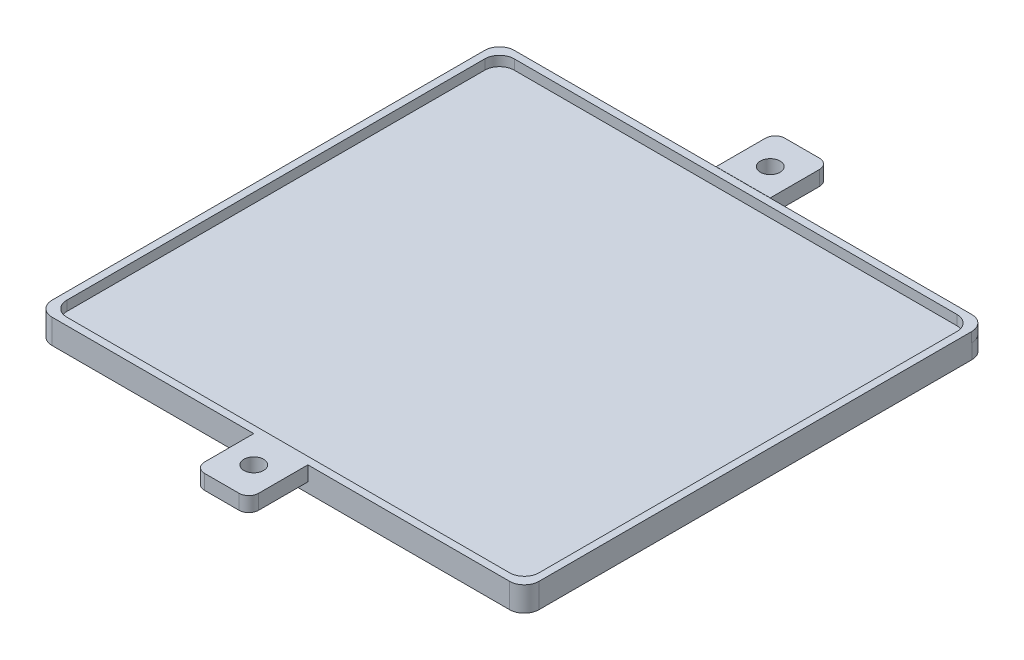
SolidWorks part; units mm, degrees
ref_plane "Plano frontal" through (0, 0, 0) normal (0, 0, 1) x (1, 0, 0)
ref_plane "Plano superior" through (0, 0, 0) normal (0, 1, 0) x (1, 0, 0)
ref_plane "Plano direito" through (0, 0, 0) normal (1, 0, 0) x (0, 0, -1)
sketch "Esboço1" plane through (0, 0, 0) normal (0, 1, 0) x (1, 0, 0)
  line L0 (0, -3) -> (93, -3)
  line L1 (0, 0) -> (93, 0) construction
  line L2 (0, 0) -> (0, 88) construction
  line L3 (0, 88) -> (93, 88) construction
  line L4 (93, 0) -> (93, 88) construction
  line L5 (-3, 0) -> (-3, 88)
  line L6 (0, 91) -> (93, 91)
  line L7 (96, 0) -> (96, 88)
  line L13 (46.5, 88) -> (46.5, 0) construction
  line L15 (0, 44) -> (93, 44) construction
  line L20 (0, 0) -> (93, 88) construction
  line L24 (96, 38.5) -> (96, 49.5)
  line L25 (43, 103) -> (50, 103)
  line L26 (41, -3) -> (52, -3)
  line L27 (41, -3) -> (41, -13)
  line L28 (43, -15) -> (50, -15)
  line L29 (52, -3) -> (52, -13)
  line L30 (52, 91) -> (52, 101)
  line L31 (41, 91) -> (52, 91)
  line L32 (41, 91) -> (41, 101)
  arc A3 (93, -3) -> (96, 0) centre (93, 0) ccw
  arc A4 (93, 91) -> (96, 88) centre (93, 88) cw
  arc A5 (-3, 88) -> (0, 91) centre (0, 88) cw
  arc A6 (0, -3) -> (-3, 0) centre (0, 0) cw
  arc A16 (50, -15) -> (52, -13) centre (50, -13) ccw
  arc A17 (41, -13) -> (43, -15) centre (43, -13) ccw
  circle A18 centre (46.5, -8.5) radius 2
  circle A19 centre (46.5, 96.5) radius 2
  arc A20 (50, 103) -> (52, 101) centre (50, 101) cw
  arc A21 (41, 101) -> (43, 103) centre (43, 101) cw
  point P15 (96, -3)
  point P24 (96, 91)
  dimension "D10" = 2
  dimension "D7" = 41
  dimension "D8" = 3
  dimension "D11" = 10
  dimension "D12" = 5.5
  dimension "D1" = 93
  dimension "D2" = 88
  dimension "D3" = 99
  dimension "D4" = 94
  dimension "D5" = 3
  dimension "D6" = 3
  dimension "D9" = 41
  dimension "D13" = 5.5
extrude "Ressalto-extrusão2" add sketch "Esboço1" along normal blind 3 contours L0 L7 L6 L5 L4 L1 L2 L3 region at (46.5, 0, -44)
extrude "Ressalto-extrusão3" add sketch "Esboço1<8>" along normal blind 3 from offset 2 contours L27 A17 L28 A16 L29 L0 A18 | A21 L32 L6 L30 A20 L25 A19 region at (46.5, 0, 3.1628) region at (41.1628, 0, -96)
sketch "Esboço1<8>" plane through (0, 0, 0) normal (0, 1, 0) x (1, 0, 0) same geometry as "Esboço1"
sketch "Esboço2" plane through (0, 3, 0) normal (0, 1, 0) x (1, 0, 0)
  line L0 (-3, 88) -> (-3, 90.9604) construction
  line L5 (-3, 90.9604) -> (-0.4856, 90.9604) construction
  line L6 (93, -3) -> (96, -3) construction
  line L7 (96, -3) -> (96, 0) construction
  line L9 (0, 90.9604) -> (93, 90.9604)
  line L10 (-3, 87.9604) -> (-3, 0)
  line L11 (0, -3) -> (93, -3)
  line L12 (96, 87.9604) -> (96, 0)
  line L13 (1.5, 89.4604) -> (91.5, 89.4604)
  line L14 (-1.5, 86.4604) -> (-1.5, 1.5)
  line L15 (1.5, -1.5) -> (91.5, -1.5)
  line L16 (94.5, 86.4604) -> (94.5, 1.5)
  arc A0 (0, 91) -> (-3, 88) centre (0, 88) ccw construction
  arc A1 (93, -3) -> (96, 0) centre (93, 0) ccw construction
  arc A6 (-3, 0) -> (0, -3) centre (0, 0) ccw
  arc A7 (0, 90.9604) -> (-3, 87.9604) centre (0, 87.9604) ccw
  arc A8 (93, 90.9604) -> (96, 87.9604) centre (93, 87.9604) cw
  arc A9 (93, -3) -> (96, 0) centre (93, 0) ccw
  arc A10 (91.5, 89.4604) -> (94.5, 86.4604) centre (91.5, 86.4604) cw
  arc A11 (91.5, -1.5) -> (94.5, 1.5) centre (91.5, 1.5) ccw
  arc A12 (-1.5, 1.5) -> (1.5, -1.5) centre (1.5, 1.5) ccw
  arc A13 (1.5, 89.4604) -> (-1.5, 86.4604) centre (1.5, 86.4604) ccw
  point P14 (95.1213, -2.1213)
  point P19 (-2.1213, 90.1213)
  dimension "D1" = 1.5
  dimension "D2" = 3
  dimension "D6" = 3
  dimension "D3" = 1.5
  dimension "D4" = 1.5
  dimension "D5" = 1.5
extrude "Ressalto-extrusão4" add sketch "Esboço2" along normal blind 2
